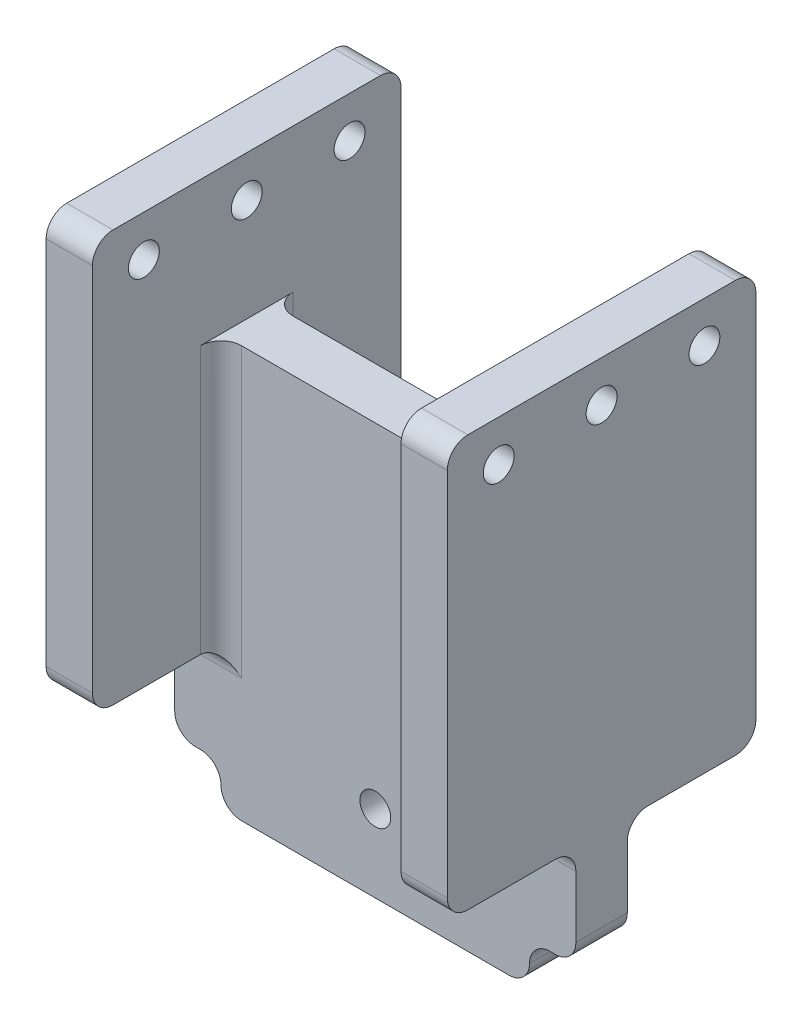
SolidWorks part; units mm, degrees
ref_plane "前视基准面" through (0, 0, 0) normal (0, 0, 1) x (1, 0, 0)
ref_plane "上视基准面" through (0, 0, 0) normal (0, 1, 0) x (1, 0, 0)
ref_plane "右视基准面" through (0, 0, 0) normal (1, 0, 0) x (0, 0, -1)
sketch "草图1" plane through (0, 0, 0) normal (0, 0, 1) x (1, 0, 0)
  line L1 (15, -25) -> (-15, -25)
  line L2 (15, -25) -> (15, 25)
  line L3 (15, 25) -> (-15, 25)
  line L4 (-15, -25) -> (-15, 25)
  line L5 (15, -25) -> (-15, 25) construction
  line L6 (15, 25) -> (-15, -25) construction
  point P0 (0, 0)
  dimension "D1" = 30
  dimension "D2" = 50
extrude "凸台-拉伸1" add sketch "草图1" along normal blind 5
sketch "草图5" plane through (-15, 0, 0) normal (-1, 0, 0) x (0, 0, 1)
  line L0 (5, 25) -> (0, 25) construction
  line L1 (17.5, 9) -> (-12.5, 9)
  line L2 (17.5, 9) -> (17.5, 59)
  line L3 (17.5, 59) -> (-12.5, 59)
  line L4 (-12.5, 9) -> (-12.5, 59)
  line L5 (17.5, 9) -> (-12.5, 59) construction
  line L6 (17.5, 59) -> (-12.5, 9) construction
  line L7 (2.5, -25) -> (2.5, 25) construction
  line L8 (5, -25) -> (0, -25) construction
  line L9 (2.5, 25) -> (2.5, 40.0267) construction
  point P0 (2.5, 34)
  dimension "D1" = 16
  dimension "D2" = 30
  dimension "D3" = 50
extrude "凸台-拉伸2" add sketch "草图5" along normal blind 4.5
mirror "镜向1" about plane through (0, 0, 0) normal (1, 0, 0) of "凸台-拉伸2"
sketch "草图6" plane through (-19.5, 0, 0) normal (-1, 0, 0) x (0, 0, 1)
  line L0 (2.5, 59) -> (2.5, 55) construction
  line L1 (17.5, 59) -> (-12.5, 59) construction
  circle A0 centre (2.5, 55) radius 1.5
  dimension "D1" = 4
  dimension "D2" = 3
extrude "切除-拉伸1" cut sketch "草图6" against normal through all
sketch "草图7" plane through (-19.5, 0, 0) normal (-1, 0, 0) x (0, 0, 1)
  line L0 (2.5, 55) -> (-7.5, 55) construction
  line L1 (2.5, 55) -> (12.5, 55) construction
  circle A0 centre (-7.5, 55) radius 1.5
  circle A1 centre (12.5, 55) radius 1.5
  dimension "D3" = 3
  dimension "D4" = 3
  dimension "D1" = 10
  dimension "D2" = 10
extrude "切除-拉伸2" cut sketch "草图7" against normal through all
sketch "草图9" plane through (0, 0, 5) normal (0, 0, 1) x (1, 0, 0)
  line L0 (0, -25) -> (0, -19) construction
  line L1 (-15, -25) -> (15, -25) construction
  circle A0 centre (0, -19) radius 1.5
  dimension "D2" = 3
  dimension "D1" = 6
sketch "草图10" plane through (0, 0, 0) normal (0, 0, -1) x (-1, 0, 0)
  line L0 (0, 1.5) -> (0, 12.5) construction
  circle A0 centre (0, 1.5) radius 1.5
  circle A1 centre (0, 12.5) radius 1.5
  dimension "D1" = 3
  dimension "D2" = 3
  dimension "D3" = 11
sketch "草图11" plane through (0, 0, 0) normal (0, 0, -1) x (-1, 0, 0)
  line L0 (-15, -25) -> (-15, 9) construction
  line L1 (15, -25) -> (-15, -25)
  line L2 (15, -25) -> (15, 3)
  line L3 (15, 3) -> (-15, 3)
  line L4 (-15, -25) -> (-15, 3)
  dimension "D1" = 28
sketch "草图12" plane through (-15, 0, 0) normal (1, 0, 0) x (0, 0, -1)
  line L0 (12.5, 59) -> (12.5, 9) construction
  line L1 (0, 9) -> (12.5, 9)
  line L2 (0, 9) -> (0, 19)
  line L3 (0, 19) -> (12.5, 19)
  line L4 (12.5, 9) -> (12.5, 19)
  line L5 (-17.5, 9) -> (-17.5, 59) construction
  line L6 (-5, 9) -> (-17.5, 9)
  line L7 (-5, 9) -> (-5, 19)
  line L8 (-5, 19) -> (-17.5, 19)
  line L9 (-17.5, 9) -> (-17.5, 19)
  dimension "D1" = 10
  dimension "D2" = 10
sketch "草图13" plane through (15, 0, 0) normal (-1, 0, 0) x (0, 0, 1)
  line L0 (17.5, 9) -> (17.5, 59) construction
  line L1 (5, 9) -> (17.5, 9)
  line L2 (5, 9) -> (5, 19)
  line L3 (5, 19) -> (17.5, 19)
  line L4 (17.5, 9) -> (17.5, 19)
  line L5 (-12.5, 59) -> (-12.5, 9) construction
  line L6 (0, 9) -> (-12.5, 9)
  line L7 (0, 9) -> (0, 19)
  line L8 (0, 19) -> (-12.5, 19)
  line L9 (-12.5, 9) -> (-12.5, 19)
  dimension "D1" = 10
  dimension "D2" = 10
sketch "草图14" plane through (0, 0, 0) normal (0, 0, -1) x (-1, 0, 0)
  line L1 (-15, -25) -> (23.6948, -25)
  line L2 (-15, -25) -> (-15, -7)
  line L3 (-15, -7) -> (23.6948, -7)
  line L4 (23.6948, -25) -> (23.6948, -7)
  dimension "D1" = 18
extrude "切除-拉伸8" cut sketch "草图12" against normal through all
extrude "切除-拉伸9" cut sketch "草图13" against normal through all
sketch "草图15" plane through (0, 0, 5) normal (0, 0, 1) x (1, 0, 0)
  circle A0 centre (0, 1.5) radius 1.25
sketch "草图16" plane through (0, 25, 0) normal (0, 1, 0) x (1, 0, 0)
  line L4 (15, 0) -> (-15, 0)
  line L5 (-15, 0) -> (-15, -5)
  line L6 (-15, -5) -> (15, -5)
  line L7 (15, -5) -> (15, 0)
  line L8 (15, 0) -> (-15, 0)
  line L9 (-15, 0) -> (-15, -5)
  line L10 (-15, -5) -> (15, -5)
  line L11 (15, -5) -> (15, 0)
  dimension "D1" = 0
extrude "凸台-拉伸3" add sketch "草图16" along normal blind 20
sketch "草图17" plane through (0, 0, 5) normal (0, 0, 1) x (1, 0, 0)
  line L0 (0, 1.5) -> (0, 12.5) construction
  circle A0 centre (0, 12.5) radius 1.5
  dimension "D1" = 3
  dimension "D2" = 11
extrude "切除-拉伸10" cut sketch "草图17" against normal blind 20
sketch "草图18" plane through (0, 0, 5) normal (0, 0, 1) x (1, 0, 0)
  line L0 (-19.5, 9) -> (-15, 9) construction
  line L1 (-20.7485, 5) -> (32.37, 5)
  line L2 (-20.7485, 5) -> (-20.7485, -43.9882)
  line L3 (-20.7485, -43.9882) -> (32.37, -43.9882)
  line L4 (32.37, 5) -> (32.37, -43.9882)
  dimension "D1" = 4
extrude "切除-拉伸11" cut sketch "草图18" against normal blind 20
fillet "圆角1" radius 2 4 edges at (-17.25, 19, 0) (17.25, 19, 0) (17.25, 19, 5) (-17.25, 19, 5)
fillet "圆角2" radius 2 4 edges at (15, 31, 0) (-15, 31, 0) (15, 31, 5) (-15, 31, 5)
fillet "圆角3" radius 2 8 edges at (-17.25, 19, 17.5) (17.25, 19, 17.5) (17.25, 59, 17.5) (-17.25, 59, 17.5) (-17.25, 59, -12.5) (17.25, 59, -12.5) (-17.25, 19, -12.5) (17.25, 19, -12.5)
fillet "圆角4" radius 2 6 edges at (15, 9, 2.5) (-15, 9, 2.5) (19.5, 9, 2.5) (15, 5, 2.5) (-15, 5, 2.5) (-19.5, 9, 2.5)
